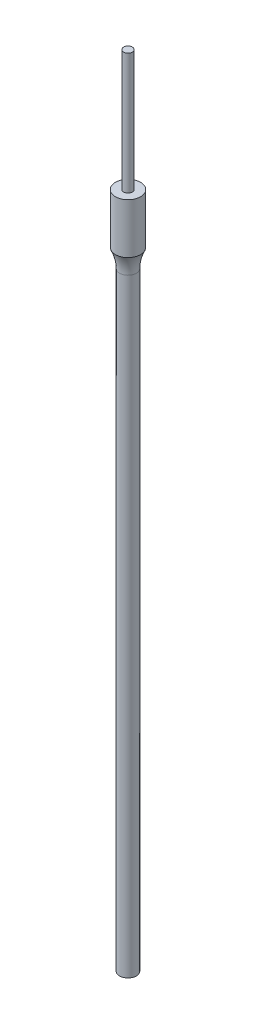
SolidWorks part; units mm, degrees
ref_plane "Front Plane" through (0, 0, 0) normal (0, 0, 1) x (1, 0, 0)
ref_plane "Top Plane" through (0, 0, 0) normal (0, 1, 0) x (1, 0, 0)
ref_plane "Right Plane" through (0, 0, 0) normal (1, 0, 0) x (0, 0, -1)
sketch "Sketch1" plane through (0, 0, 0) normal (0, 1, 0) x (1, 0, 0)
  circle A0 centre (0, 0) radius 2
  dimension "D1" = 4
extrude "Boss-Extrude1" add sketch "Sketch1" along normal blind 150
sketch "Sketch2" plane through (0, 150, 0) normal (0, 1, 0) x (1, 0, 0)
  circle A0 centre (0, 0) radius 3
  dimension "D1" = 6
extrude "Boss-Extrude2" add sketch "Sketch2" along normal blind 12
fillet "Fillet1" radius 10 1 edges at (0, 150, 2)
sketch "Sketch3" plane through (0, 162, 0) normal (0, 1, 0) x (1, 0, 0)
  circle A0 centre (0, 0) radius 1.0483
extrude "Boss-Extrude3" add sketch "Sketch3" along normal blind 29 separate body
